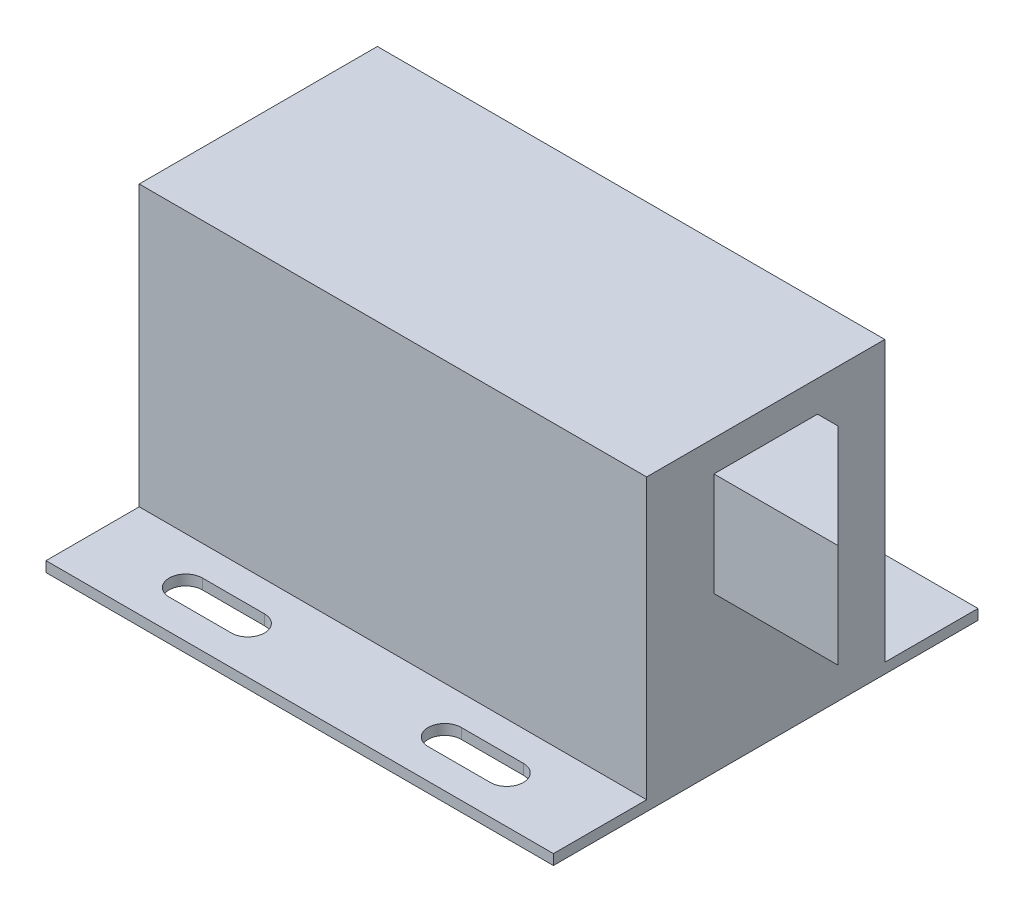
SolidWorks part; units mm, degrees
ref_plane "Front Plane" through (0, 0, 0) normal (0, 0, 1) x (1, 0, 0)
ref_plane "Top Plane" through (0, 0, 0) normal (0, 1, 0) x (1, 0, 0)
ref_plane "Right Plane" through (0, 0, 0) normal (1, 0, 0) x (0, 0, -1)
sketch "Sketch1" plane through (0, 0, 0) normal (0, 1, 0) x (1, 0, 0)
  line L0 (9, 36.5) -> (15, 36.5) construction
  line L1 (0, 0) -> (49, 0)
  line L2 (0, 0) -> (0, 41)
  line L3 (0, 41) -> (49, 41)
  line L4 (49, 0) -> (49, 41)
  line L5 (9, 38.1) -> (15, 38.1)
  line L6 (9, 34.9) -> (15, 34.9)
  line L7 (34, 36.5) -> (40, 36.5) construction
  line L8 (34, 38.1) -> (40, 38.1)
  line L9 (34, 34.9) -> (40, 34.9)
  line L10 (34, 4.5) -> (40, 4.5) construction
  line L11 (34, 6.1) -> (40, 6.1)
  line L12 (34, 2.9) -> (40, 2.9)
  line L13 (15, 4.5) -> (9, 4.5) construction
  line L14 (15, 2.9) -> (9, 2.9)
  line L15 (15, 6.1) -> (9, 6.1)
  line L16 (24.5, 41) -> (24.5, 0) construction
  line L17 (0, 20.5) -> (49, 20.5) construction
  arc A0 (9, 38.1) -> (9, 34.9) centre (9, 36.5) ccw
  arc A1 (15, 34.9) -> (15, 38.1) centre (15, 36.5) ccw
  arc A2 (34, 38.1) -> (34, 34.9) centre (34, 36.5) ccw
  arc A3 (40, 34.9) -> (40, 38.1) centre (40, 36.5) ccw
  arc A4 (34, 6.1) -> (34, 2.9) centre (34, 4.5) ccw
  arc A5 (40, 2.9) -> (40, 6.1) centre (40, 4.5) ccw
  arc A6 (15, 2.9) -> (15, 6.1) centre (15, 4.5) ccw
  arc A7 (9, 6.1) -> (9, 2.9) centre (9, 4.5) ccw
  point P7 (12, 36.5)
  point P14 (37, 36.5)
  point P19 (37, 4.5)
  point P26 (12, 4.5)
  dimension "D3" = 1.6
  dimension "D1" = 49
  dimension "D2" = 41
  dimension "D4" = 25
  dimension "D5" = 32
  dimension "D6" = 6
extrude "Boss-Extrude1" add sketch "Sketch1" along normal blind 1
sketch "Sketch2" plane through (0, 1, 0) normal (0, 1, 0) x (1, 0, 0)
  line L0 (0, 41) -> (0, 0) construction
  line L1 (0, 32) -> (49, 32)
  line L2 (0, 32) -> (0, 9)
  line L3 (0, 9) -> (49, 9)
  line L4 (49, 32) -> (49, 9)
  line L5 (49, 0) -> (49, 41) construction
  line L6 (0, 20.5) -> (49, 20.5) construction
  dimension "D1" = 23
extrude "Boss-Extrude2" add sketch "Sketch2" along normal blind 27
sketch "Sketch3" plane through (49, 0, 0) normal (1, 0, 0) x (0, 0, -1)
  line L0 (9, 28) -> (9, 1) construction
  line L1 (15.5, 15) -> (25.5, 15)
  line L2 (15.5, 15) -> (15.5, 25)
  line L3 (15.5, 25) -> (25.5, 25)
  line L4 (25.5, 15) -> (25.5, 25)
  line L5 (0, 1) -> (9, 1) construction
  dimension "D1" = 10
  dimension "D2" = 10
  dimension "D3" = 6.5
  dimension "D4" = 14
extrude "Boss-Extrude3" add sketch "Sketch3" along normal blind 12
chamfer "Chamfer1" distance 10 angle 45 1 edges at (61, 20, -25.5)
